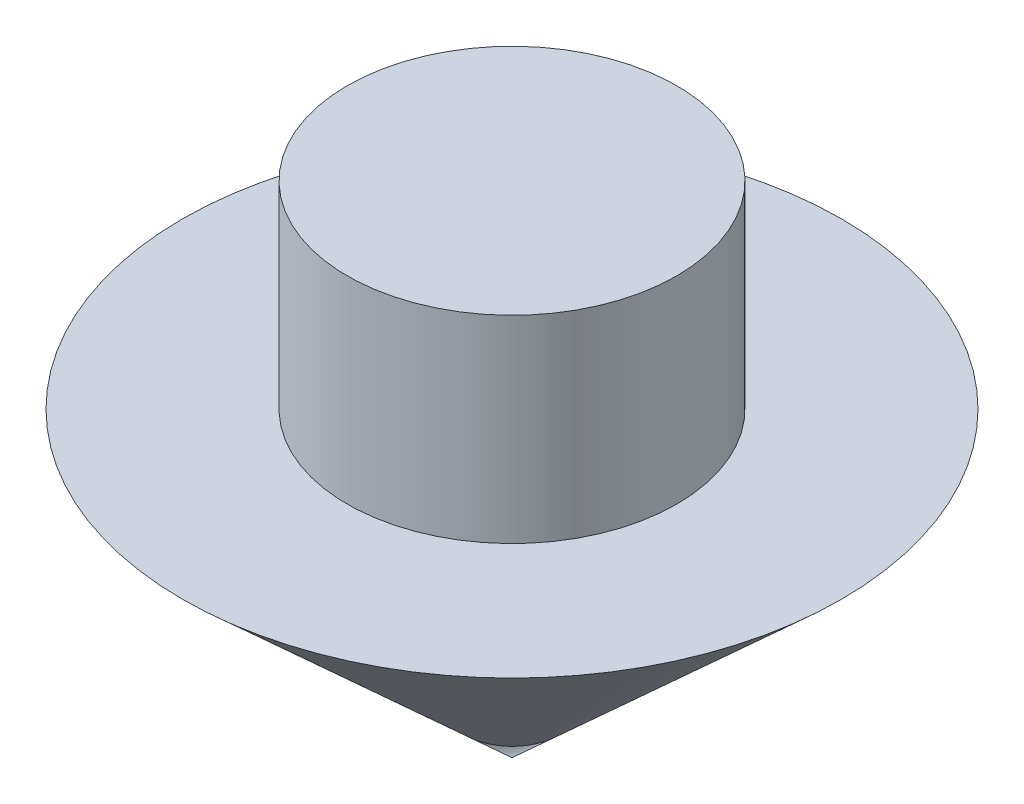
SolidWorks part; units mm, degrees
material "3003 Alloy"
ref_plane "Front Plane" through (0, 0, 0) normal (0, 0, 1) x (1, 0, 0)
ref_plane "Top Plane" through (0, 0, 0) normal (0, 1, 0) x (1, 0, 0)
ref_plane "Right Plane" through (0, 0, 0) normal (1, 0, 0) x (0, 0, -1)
sketch "Sketch1" plane through (0, 0, 0) normal (0, 0, 1) x (1, 0, 0)
  line L0 (0, 0) -> (10, 9.1633)
  line L1 (10, 9.1633) -> (-10, 9.1633)
  line L2 (-10, 9.1633) -> (0, 0)
  line L3 (0, 0) -> (0, 9.1633)
  dimension "D1" = 20
  dimension "D2" = 47.5
revolve "Revolve1" add sketch "Sketch1" angle 360 about L3 region at (3.3333, 6.1089, 0)
ref_axis "Axis1" through (0, 0, 0) along (0, 1, 0)
sketch "Sketch2" plane through (0, 0, 0) normal (0, 0, 1) x (1, 0, 0)
  line L0 (10, 9.1633) -> (-10, 9.1633) construction
  line L1 (0, 9.1633) -> (5, 9.1633)
  line L2 (0, 9.1633) -> (0, 15.1633)
  line L3 (0, 15.1633) -> (5, 15.1633)
  line L4 (5, 9.1633) -> (5, 15.1633)
  dimension "D1" = 6
  dimension "D2" = 5
revolve "Revolve2" add sketch "Sketch2" angle 360 about axis through (0, 0, 0) along (0, 1, 0) region at (2.5, 12.1633, 0)
